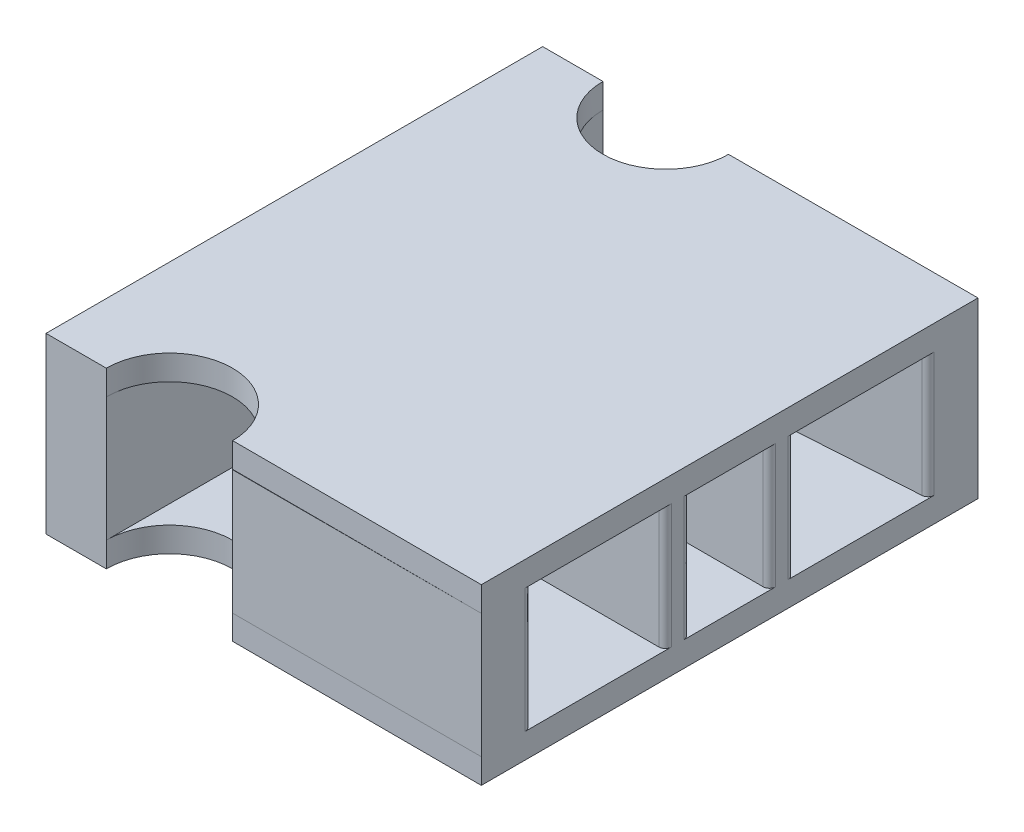
SolidWorks part; units mm, degrees
ref_plane "Alzado" through (0, 0, 0) normal (0, 0, 1) x (1, 0, 0)
ref_plane "Planta" through (0, 0, 0) normal (0, 1, 0) x (1, 0, 0)
ref_plane "Vista lateral" through (0, 0, 0) normal (1, 0, 0) x (0, 0, -1)
sketch "Croquis1" plane through (0, 0, 0) normal (0, 1, 0) x (1, 0, 0)
  line L0 (-17.5304, 19.9991) -> (17.5304, 19.9991) construction
  line L1 (17.5304, 19.9991) -> (-2.4991, 19.9991)
  line L2 (-17.5304, 19.9991) -> (-17.5304, -20.0009) construction
  line L3 (-17.5304, -20.0009) -> (17.5304, -20.0009) construction
  line L4 (17.5304, -20.0009) -> (17.5304, -15.9974) construction
  line L5 (-2.4991, 19.9991) -> (-2.5304, 19.9681)
  line L6 (-2.5304, 19.9681) -> (-2.5304, 14.7182)
  line L7 (-2.5304, 14.7182) -> (17.5304, 16.0003)
  line L8 (17.5304, 16.0003) -> (17.5304, 19.9991)
  line L9 (17.5304, -20.0009) -> (-2.4991, -20.0009)
  line L10 (-2.4991, -20.0009) -> (-2.5305, -19.9696)
  line L11 (-2.5305, -19.9696) -> (-2.5305, -14.7108)
  line L12 (-2.5305, -14.7108) -> (17.5304, -15.9974)
  line L13 (17.5304, -15.9974) -> (17.5304, -20.0009)
  line L14 (-12.6701, 19.9991) -> (-17.5304, 19.9991)
  line L15 (-17.5304, 19.9991) -> (-17.5304, -20.0009)
  line L16 (-17.5304, -20.0009) -> (-12.6701, -20.0009)
  line L17 (-12.6701, 19.9991) -> (-12.6701, -20.0009)
  line L20 (17.5304, 16.0003) -> (17.5304, 19.9991) construction
  line L21 (17.5293, 16.0182) -> (17.5293, -16.0152) construction
extrude "Saliente-Extruir1" add sketch "Croquis1" along normal mid plane 10
sketch "Croquis3" plane through (0, 5, 0) normal (0, 1, 0) x (1, 0, 0)
  line L0 (-17.5304, 19.9991) -> (-12.6701, 19.9991)
  line L1 (-17.5304, 19.9991) -> (-17.5304, -20.0009)
  line L2 (-17.5304, -20.0009) -> (-12.6701, -20.0009)
  line L3 (-2.5305, -19.9696) -> (17.5304, -20.0009)
  line L4 (17.5304, -20.0009) -> (17.5304, 19.9991)
  line L5 (17.5304, 19.9991) -> (-2.5304, 19.9681)
  arc A2 (-12.6701, 19.9991) -> (-2.5304, 19.9681) centre (-7.6002, 19.9836) ccw
  arc A3 (-12.6701, -20.0009) -> (-2.5305, -19.9696) centre (-7.6003, -19.9852) cw
extrude "Saliente-Extruir2" add sketch "Croquis3" along normal blind 2
mirror "Simetría1" about plane through (0, 0, 0) normal (0, 1, 0) of "Saliente-Extruir2"
fillet "Redondeo1" radius 0.5 1 edges at (-2.5305, 0, 14.7108)
fillet "Redondeo2" radius 0.5 1 edges at (-2.5304, 0, -14.7182)
fillet "Redondeo3" radius 0.5 2 edges at (17.5304, 0, -16.0003) (17.5304, 0, 15.9974)
sketch "Croquis5" plane through (0, 0, 0) normal (0, 1, 0) x (1, 0, 0)
  line L0 (17.5304, -5.1985) -> (17.5304, -3.1985)
  line L1 (17.5304, -16.4663) -> (17.5304, 16.4693) construction
  line L2 (17.5304, 3.2015) -> (-12.6701, 3.2015)
  line L3 (-12.6701, -19.9696) -> (-12.6701, 19.9681) construction
  line L4 (-12.6701, 3.2015) -> (-12.6701, 5.2015)
  line L5 (-12.6701, 5.2015) -> (17.5304, 5.2015)
  line L6 (17.5304, 5.2015) -> (17.5304, 3.2015)
  line L7 (18.3108, 0.0015) -> (-25.4962, 0.0015) construction
  line L8 (-12.6701, -5.1985) -> (17.5304, -5.1985)
  line L9 (-12.6701, -3.1985) -> (-12.6701, -5.1985)
  line L10 (17.5304, -3.1985) -> (-12.6701, -3.1985)
  point P5 (17.5304, 0.0015)
  dimension "D1" = 6.4
  dimension "D2" = 2
extrude "Saliente-Extruir3" add sketch "Croquis5" along normal mid plane 10
fillet "Redondeo4" radius 0.5 4 edges at (17.5304, 0, -5.2015) (17.5304, 0, -3.2015) (17.5304, 0, 3.1985) (17.5304, 0, 5.1985)
